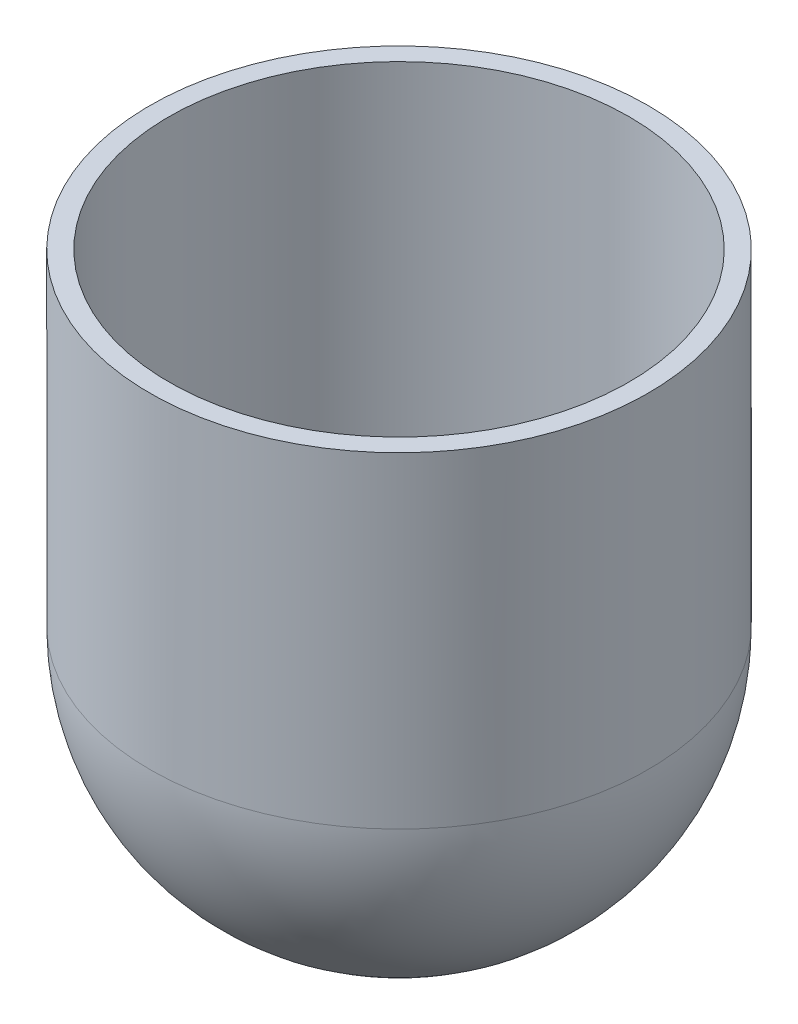
SolidWorks part; units mm, degrees
ref_plane "Front Plane" through (0, 0, 0) normal (0, 0, 1) x (1, 0, 0)
ref_plane "Top Plane" through (0, 0, 0) normal (0, 1, 0) x (1, 0, 0)
ref_plane "Right Plane" through (0, 0, 0) normal (1, 0, 0) x (0, 0, -1)
sketch "Sketch1" plane through (0, 0, 0) normal (0, 1, 0) x (1, 0, 0)
  circle A0 centre (0, 0) radius 38.1
  dimension "D1" = 76.2
extrude "Boss-Extrude1" add sketch "Sketch1" along normal blind 50.8275
ref_axis "Axis1" through (0, 50.8275, 0) along (0, -1, 0)
shell "Shell2" thickness 3.175 removed face at (0, 50.8275, 38.1) outward yes
sketch "Sketch5" plane through (0, -3.175, 0) normal (0, -1, 0) x (1, 0, 0)
  line L0 (-40.4451, 8.2352) -> (40.4451, -8.2352)
  arc A0 (40.4451, -8.2352) -> (-40.4451, 8.2352) centre (0, 0) cw
  circle A1 centre (0, 0) radius 41.275 construction
revolve "Revolve1" add sketch "Sketch5" angle 180 about L0 reverse direction yes
shell "Shell4" thickness 3.175 removed face at (0, 0, 38.1)
scale "Scale1" scale about centroid uniform scaling yes scale factor 0.615385
